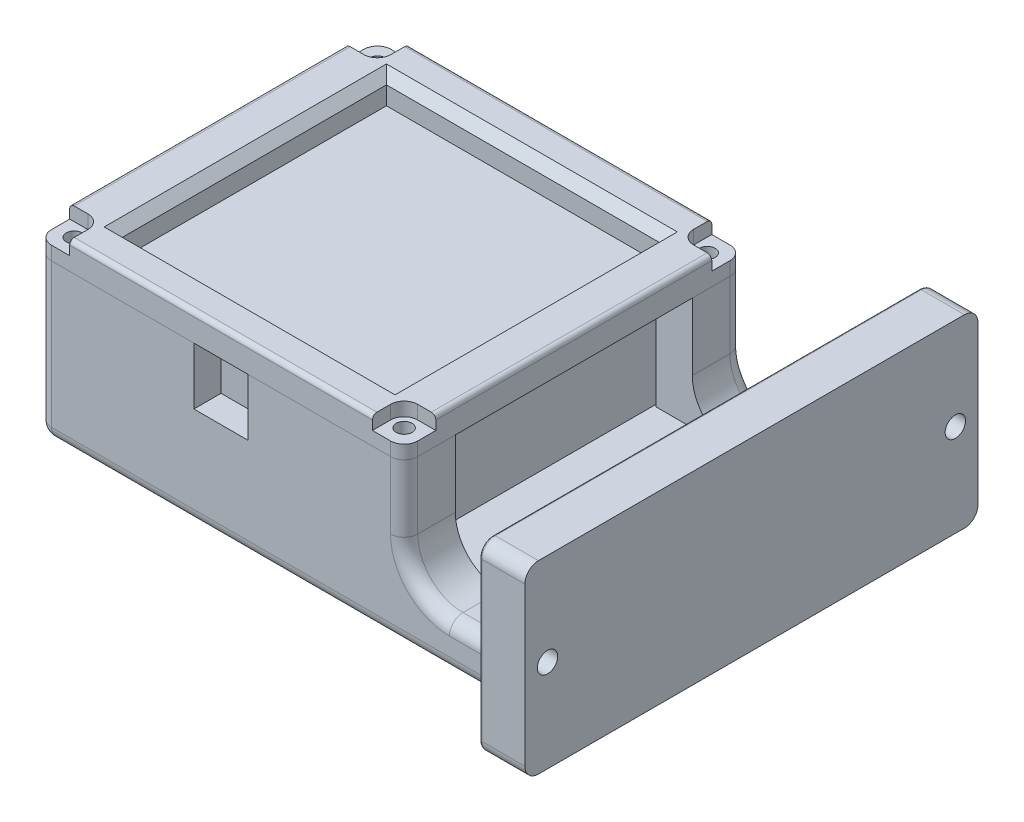
SolidWorks part; units mm, degrees
ref_plane "正面" through (0, 0, 0) normal (0, 0, 1) x (1, 0, 0)
ref_plane "平面" through (0, 0, 0) normal (0, 1, 0) x (1, 0, 0)
ref_plane "右側面" through (0, 0, 0) normal (1, 0, 0) x (0, 0, -1)
sketch "ｽｹｯﾁ1" plane through (0, 0, 0) normal (0, 1, 0) x (1, 0, 0)
  line L1 (-32.1, 31.15) -> (32.1, 31.15)
  line L2 (-32.1, 31.15) -> (-32.1, -31.15)
  line L3 (-32.1, -31.15) -> (32.1, -31.15)
  line L4 (32.1, 31.15) -> (32.1, -31.15)
  point P4 (0, 31.15)
  point P6 (-32.1, 0)
  dimension "D1" = 64.2
  dimension "D2" = 62.3
extrude "本体" add sketch "ｽｹｯﾁ1" along normal mid plane 24.2
sketch "ｽｹｯﾁ2" plane through (0, 0, 0) normal (0, -1, 0) x (1, 0, 0)
  line L0 (0, -37.45) -> (0, 0) construction
  line L1 (32.4, -26.15) -> (32.4, -31.45)
  line L2 (40.4, -26.15) -> (32.4, -26.15)
  line L3 (-40.4, -37.45) -> (40.4, -37.45)
  line L4 (40.4, -26.15) -> (40.4, -37.45)
  line L5 (32.1, -31.15) -> (-32.1, -31.15) construction
  line L7 (-40.4, -26.15) -> (-32.4, -26.15)
  line L12 (0, 0) -> (-40.4, 0) construction
  line L14 (-40.4, -26.15) -> (-40.4, -37.45)
  line L15 (32.4, 26.15) -> (32.4, 31.45)
  line L16 (-32.4, 31.45) -> (-32.4, -31.45)
  line L17 (32.4, 31.45) -> (-32.4, 31.45)
  line L18 (32.4, -31.45) -> (32.4, 31.45)
  line L19 (-32.4, -31.45) -> (32.4, -31.45)
  line L20 (-32.4, -26.15) -> (-32.4, -31.45)
  line L21 (40.4, 26.15) -> (32.4, 26.15)
  line L22 (40.4, 26.15) -> (40.4, 37.45)
  line L23 (-32.4, -31.45) -> (32.4, -31.45)
  line L24 (-32.4, 31.45) -> (32.4, 31.45)
  line L25 (-32.4, 26.15) -> (-32.4, 31.45)
  line L26 (-40.4, 26.15) -> (-32.4, 26.15)
  line L27 (-40.4, 26.15) -> (-40.4, 37.45)
  line L28 (-40.4, 37.45) -> (40.4, 37.45)
  circle A0 centre (-36.4, -33.45) radius 4 construction
  circle A1 centre (-36.4, -33.45) radius 1.1
  circle A2 centre (36.4, -33.45) radius 1.1
  circle A3 centre (36.4, 33.45) radius 1.1
  circle A4 centre (-36.4, 33.45) radius 1.1
  point P16 (0, -31.45)
  dimension "D1" = 8
  dimension "D2" = 2.2
  dimension "D4" = 5
  dimension "D5" = 6
  dimension "D6" = 11.3
  dimension "D3" = 0.3
extrude "ﾎﾞｽ - 押し出し2" add sketch "ｽｹｯﾁ2" against normal offset from surface 0.4 and the other way offset from surface (12.3 mm away) 0.2 separate body up to face at (0, 12.1, 0) offset beyond the face yes other way up to face at (0, -12.1, 0)
sketch "ｽｹｯﾁ3" plane through (0, 0, 0) normal (0, 0, 1) x (1, 0, 0)
  line L0 (-32.1, -12.1) -> (32.1, -12.1) construction
  line L1 (-6, 12.5) -> (6, 12.5)
  line L2 (-6, 12.5) -> (-6, -0.1)
  line L3 (-6, -0.1) -> (6, -0.1)
  line L4 (6, 12.5) -> (6, -0.1)
  line L5 (-32.1, 12.1) -> (32.1, 12.1) construction
  line L6 (40.4, 12.5) -> (-40.4, 12.5) construction
  point P8 (0, 12.1)
  point P9 (0, 12.5)
  dimension "D1" = 12
  dimension "D2" = 12
extrude "ｶｯﾄ - 押し出し1" cut sketch "ｽｹｯﾁ3" against normal through all both and the other way through all
sketch "ｽｹｯﾁ8" plane through (0, 0, 0) normal (0, 0, 1) x (1, 0, 0)
  line L0 (40.4, 0.1) -> (69.6, 0.1) construction
  line L1 (-40.4, -12.3) -> (69.6, -12.3)
  line L2 (-40.4, -12.3) -> (-40.4, -22.3)
  line L3 (-40.4, -22.3) -> (69.6, -22.3)
  line L4 (40.4, 12.5) -> (40.4, -12.3) construction
  line L5 (-40.4, 12.5) -> (-40.4, -12.3) construction
  line L6 (69.6, -22.3) -> (69.6, -12.3)
  point P5 (79.6, -12.3)
  point P11 (0, 0)
  point P12 (52.6595, 13.6808)
  point P15 (79.6, -11.5878)
  dimension "D1" = 10
  dimension "D3" = 110
extrude "ﾎﾞｽ - 押し出し6" add sketch "ｽｹｯﾁ8" along normal up to vertex (37.45 mm away) and the other way up to vertex (37.45 mm away) up to point (40.4, -12.3, 37.45) other way up to point (40.4, -12.3, -37.45)
sketch "ｽｹｯﾁ4" plane through (0, -12.3, 0) normal (0, 1, 0) x (-1, 0, 0)
  line L1 (-52.45, 37.45) -> (52.45, 37.45)
  line L2 (-52.45, 37.45) -> (-52.45, 25.45)
  line L3 (-52.45, 25.45) -> (52.45, 25.45)
  line L4 (52.45, 37.45) -> (52.45, 25.45)
  line L8 (32.1, 0) -> (0, 0) construction
  line L9 (32.1, -31.15) -> (32.1, 31.15) construction
  line L10 (0, 0) -> (0, -31.15) construction
  line L11 (-32.1, -31.15) -> (32.1, -31.15) construction
  line L12 (52.45, -37.45) -> (52.45, -25.45)
  line L13 (-52.45, -25.45) -> (52.45, -25.45)
  line L14 (-52.45, -37.45) -> (-52.45, -25.45)
  line L15 (-52.45, -37.45) -> (52.45, -37.45)
  line L16 (32.1, -25.45) -> (32.1, 25.45)
  line L17 (-32.1, -25.45) -> (-32.1, 25.45)
  circle A0 centre (-45, 30) radius 7.45 construction
  circle A1 centre (-45, 30) radius 4 construction
  circle A2 centre (-45, 30) radius 2.1
  circle A3 centre (45, 30) radius 2.1
  circle A4 centre (-45, -30) radius 4 construction
  circle A5 centre (-45, -30) radius 7.45 construction
  circle A6 centre (45, -30) radius 2.1
  circle A7 centre (-45, -30) radius 2.1
  dimension "D3" = 12
  dimension "D4" = 8
  dimension "D5" = 4.2
  dimension "D6" = 60
  dimension "D7" = 90
extrude "ﾎﾞｽ - 押し出し3" [suppressed] add sketch "ｽｹｯﾁ4" along normal blind 6.5 separate body
sketch "ｽｹｯﾁ7" [suppressed] plane through (0, -12.3, 0) normal (0, 1, 0) x (1, 0, 0)
  line L0 (32.1, 25.45) -> (32.1, -25.45) construction
  line L1 (-17.1, 21.45) -> (17.1, 21.45)
  line L2 (-22.1, 16.45) -> (-22.1, -16.45)
  line L3 (-17.1, -21.45) -> (17.1, -21.45)
  line L4 (22.1, 16.45) -> (22.1, -16.45)
  line L5 (-32.4, 31.45) -> (32.4, 31.45) construction
  arc A0 (-22.1, -16.45) -> (-17.1, -21.45) centre (-17.1, -16.45) ccw
  arc A1 (17.1, -21.45) -> (22.1, -16.45) centre (17.1, -16.45) ccw
  arc A2 (17.1, 21.45) -> (22.1, 16.45) centre (17.1, 16.45) cw
  arc A3 (-17.1, 21.45) -> (-22.1, 16.45) centre (-17.1, 16.45) ccw
  point P4 (0, -21.45)
  point P6 (-22.1, 0)
  dimension "D3" = 5
  dimension "D1" = 10
  dimension "D2" = 10
extrude "ｶｯﾄ - 押し出し2" [suppressed] cut sketch "ｽｹｯﾁ7" against normal through all
sketch "ｽｹｯﾁ5" plane through (0, 12.5, 0) normal (0, 1, 0) x (1, 0, 0)
  line L1 (-40.4, 37.45) -> (40.4, 37.45)
  line L2 (-40.4, 37.45) -> (-40.4, -37.45)
  line L3 (-40.4, -37.45) -> (40.4, -37.45)
  line L4 (40.4, 37.45) -> (40.4, -37.45)
  line L13 (-30.1, 29.15) -> (-30.1, -29.15)
  line L14 (-30.1, -29.15) -> (30.1, -29.15)
  line L15 (30.1, -29.15) -> (30.1, 29.15)
  line L16 (30.1, 29.15) -> (-30.1, 29.15)
  line L17 (-30.1, 29.15) -> (-30.1, -29.15)
  line L18 (-30.1, -29.15) -> (30.1, -29.15)
  line L19 (30.1, -29.15) -> (30.1, 29.15)
  line L20 (30.1, 29.15) -> (-30.1, 29.15)
  circle A0 centre (-36.4, 33.45) radius 1.75
  circle A1 centre (36.4, 33.45) radius 1.75
  circle A2 centre (36.4, -33.45) radius 1.75
  circle A3 centre (-36.4, -33.45) radius 1.75
  dimension "D1" = 3.5
  dimension "D2" = 2
extrude "ﾎﾞｽ - 押し出し4" add sketch "ｽｹｯﾁ5" along normal blind 3 separate body
sketch "ｽｹｯﾁ6" plane through (0, 15.5, 0) normal (0, 1, 0) x (1, 0, 0)
  line L1 (33.4, 30.45) -> (40.4, 30.45)
  line L2 (-40.4, 37.45) -> (-33.4, 37.45)
  line L3 (-40.4, 37.45) -> (-40.4, 30.45)
  line L4 (-40.4, 30.45) -> (-33.4, 30.45)
  line L5 (-33.4, 37.45) -> (-33.4, 30.45)
  line L6 (33.4, 37.45) -> (40.4, 37.45)
  line L7 (33.4, 37.45) -> (33.4, 30.45)
  line L8 (40.4, 37.45) -> (40.4, 30.45)
  line L9 (33.4, -37.45) -> (40.4, -37.45)
  line L10 (33.4, -30.45) -> (40.4, -30.45)
  line L11 (33.4, -30.45) -> (33.4, -37.45)
  line L12 (40.4, -30.45) -> (40.4, -37.45)
  line L13 (-40.4, -37.45) -> (-33.4, -37.45)
  line L14 (-40.4, -30.45) -> (-33.4, -30.45)
  line L15 (-40.4, -30.45) -> (-40.4, -37.45)
  line L16 (-33.4, -30.45) -> (-33.4, -37.45)
  line L18 (40.4, -37.45) -> (40.4, 37.45) construction
  line L19 (40.4, 37.45) -> (-40.4, 37.45) construction
  line L20 (-40.4, 37.45) -> (-40.4, -37.45) construction
  line L22 (-40.4, -37.45) -> (40.4, -37.45) construction
  circle A0 centre (-36.4, 33.45) radius 3
  circle A1 centre (36.4, 33.45) radius 3
  circle A2 centre (36.4, -33.45) radius 3
  circle A3 centre (-36.4, -33.45) radius 3
  line M5 (-40.4, 37.45) -> (-40.4, -37.45)
  line M6 (-40.4, -37.45) -> (40.4, -37.45)
  line M7 (40.4, -37.45) -> (40.4, 37.45)
  line M8 (40.4, 37.45) -> (-40.4, 37.45)
  line M11 (-30.1, -29.15) -> (-30.1, 29.15)
  line M12 (-30.1, 29.15) -> (30.1, 29.15)
  line M13 (30.1, 29.15) -> (30.1, -29.15)
  line M14 (30.1, -29.15) -> (-30.1, -29.15)
  dimension "D1" = 6
extrude "ﾎﾞｽ - 押し出し5" add sketch "ｽｹｯﾁ6" along normal blind 3 contours L14 L16 L11 L10 L1 L7 L5 L4 M6 M7 M8 M5 M14 M11 M12 M13 | A0 L4 L5 | A1 L7 L1 | A2 L10 L11 | A3 L16 L14
sketch "ｽｹｯﾁ10" plane through (69.6, 0, 0) normal (1, 0, 0) x (0, 0, -1)
  line L0 (-37.45, -22.3) -> (37.45, -22.3) construction
  line L1 (-50, -22.3) -> (50, -22.3)
  line L2 (-50, -22.3) -> (-50, 18.5)
  line L3 (-50, 18.5) -> (50, 18.5)
  line L4 (50, -22.3) -> (50, 18.5)
  line L5 (-30.45, 18.5) -> (30.45, 18.5) construction
  line L6 (-50, -1.9) -> (50, -1.9) construction
  line L7 (0, 18.5) -> (0, -22.3) construction
  circle A0 centre (45, -1.9) radius 2.25
  circle A1 centre (-45, -1.9) radius 2.25
  point P7 (0, -22.3)
  dimension "D2" = 4.5
  dimension "D1" = 100
  dimension "D3" = 90
extrude "ﾎﾞｽ - 押し出し8" add sketch "ｽｹｯﾁ10" along normal blind 10
fillet "ﾌｨﾚｯﾄ6" radius 10 3 edges at (69.6, -12.3, 0) (40.4, -12.3, -31.8) (40.4, -12.3, 31.8)
fillet "ﾌｨﾚｯﾄ5" radius 3 9 edges at (74.6, 18.5, -50) (74.6, -22.3, -50) (74.6, 18.5, 50) (74.6, -22.3, 50) (14.6, -22.3, -37.45) (14.6, -22.3, 37.45) (-40.4, -22.3, 0) (-40.4, -4.9, -37.45) (-40.4, -4.9, 37.45)
chamfer "面取り1" distance 2 angle 45 4 edges at (0, 18.5, 29.15) (0, 18.5, -29.15) (-30.1, 18.5, 0) (30.1, 18.5, 0)
fillet "ﾌｨﾚｯﾄ1" radius 3 4 edges at (-40.4, 14, -37.45) (-40.4, 14, 37.45) (40.4, 14, 37.45) (40.4, 14, -37.45)
fillet "ﾌｨﾚｯﾄ4" radius 1 4 edges at (0, 18.5, 37.45) (40.4, 18.5, 0) (0, 18.5, -37.45) (-40.4, 18.5, 0)
fillet "ﾌｨﾚｯﾄ2" [suppressed] radius 3
fillet "ﾌｨﾚｯﾄ8" radius 3 8 edges at (66.6711, -9.3711, -37.45) (55, -12.3, -37.45) (43.3289, -9.3711, -37.45) (66.6711, -9.3711, 37.45) (55, -12.3, 37.45) (43.3289, -9.3711, 37.45) (40.4, 5.1, -37.45) (40.4, 5.1, 37.45)
fillet "ﾌｨﾚｯﾄ7" radius 0.5 15 edges at (69.6, -21.4213, -36.5713) (69.6, -22.3, -40.725) (69.6, -21.4213, -49.1213) (69.6, -1.9, -50) (69.6, 17.6213, -49.1213) (69.6, 18.5, 0) (69.6, 17.6213, 49.1213) (69.6, -22.3, 40.725) (69.6, -21.4213, 49.1213) (69.6, -21.4213, 36.5713) (69.6, -14.9533, -37.45) (69.6, -1.9, 50) (69.6, -14.9533, 37.45) (69.6, -7.7683, -36.9861) (69.6, -7.7683, 36.9861)
